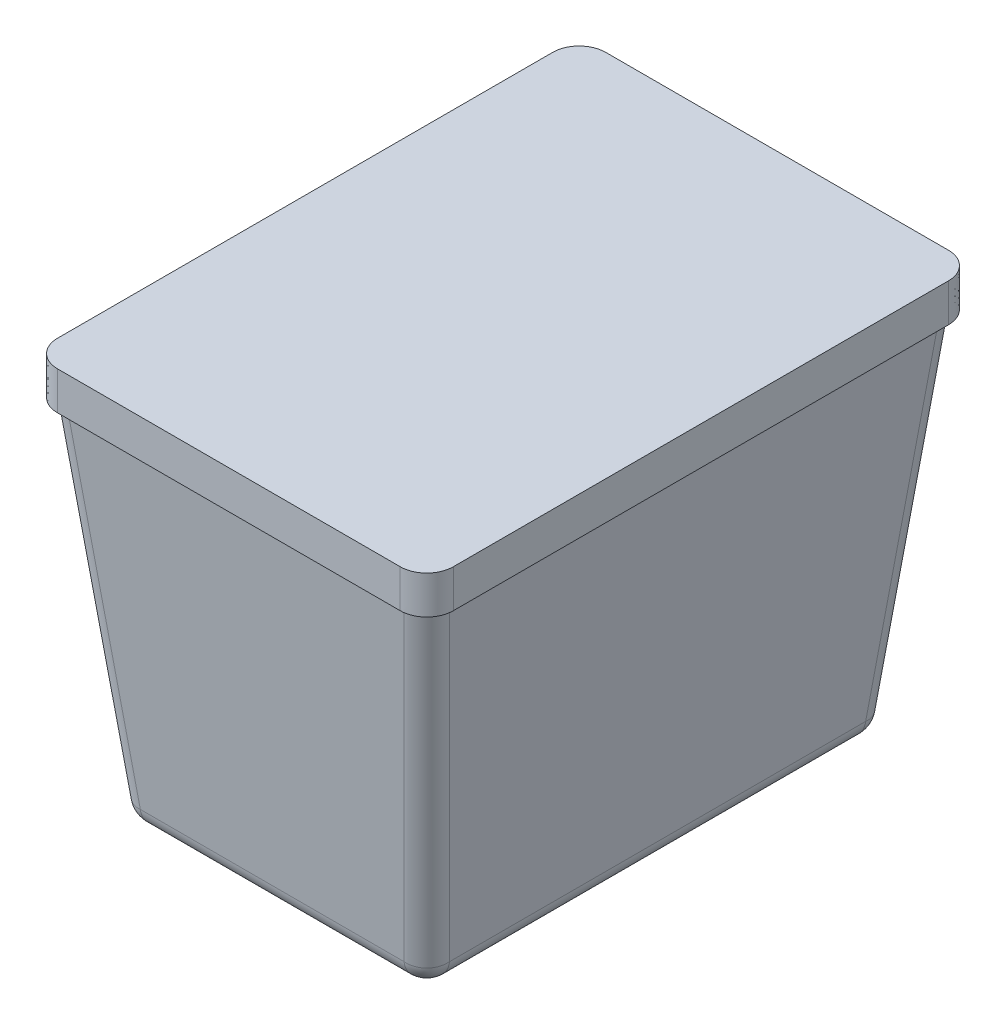
SolidWorks part; units mm, degrees
ref_plane "Alzado" through (0, 0, 0) normal (0, 0, 1) x (1, 0, 0)
ref_plane "Planta" through (0, 0, 0) normal (0, 1, 0) x (1, 0, 0)
ref_plane "Vista lateral" through (0, 0, 0) normal (1, 0, 0) x (0, 0, -1)
sketch "Croquis1" plane through (0, 0, 0) normal (0, 1, 0) x (1, 0, 0)
  line L1 (200, -300) -> (-200, -300)
  line L2 (200, -300) -> (200, 300)
  line L3 (200, 300) -> (-200, 300)
  line L4 (-200, -300) -> (-200, 300)
  line L5 (200, -300) -> (-200, 300) construction
  line L6 (200, 300) -> (-200, -300) construction
  point P0 (0, 0)
  dimension "D1" = 600
  dimension "D2" = 400
extrude "Extruir1" add sketch "Croquis1" along normal blind 520 draft 6 draft outward yes
fillet "Redondeo1" radius 30 8 edges at (0, 0, 300) (200, 0, 0) (0, 0, -300) (-200, 0, 0) (-227.3271, 260, -327.3271) (227.3271, 260, -327.3271) (227.3271, 260, 327.3271) (-227.3271, 260, 327.3271)
shell "Vaciado1" thickness 10 removed face at (0, 520, 0)
sketch "Croquis2" plane through (0, 520, 0) normal (0, 1, 0) x (1, 0, 0)
  line L24 (224.8185, 359.6542) -> (-224.8185, 359.6542)
  line L25 (259.6542, -324.8185) -> (259.6542, 324.8185)
  line L26 (-224.8185, -359.6542) -> (224.8185, -359.6542)
  line L27 (-259.6542, 324.8185) -> (-259.6542, -324.8185)
  line L28 (224.8185, 359.6542) -> (-224.8185, 359.6542)
  line L29 (259.6542, -324.8185) -> (259.6542, 324.8185)
  line L30 (-224.8185, -359.6542) -> (224.8185, -359.6542)
  line L31 (-259.6542, 324.8185) -> (-259.6542, -324.8185)
  spline S0 degree 3 poles (409.626, -1532.0878) (32.0766, -0.852) (-135.9095, 377.862) (-232.7137, 358.7732) (-233.8149, 358.5002) (-235.4515, 358.0079) (-235.9946, 357.83) (-237.0755, 357.446) (-237.6138, 357.2397) (-240.2615, 356.1489) (-242.2653, 355.0812) (-245.1032, 353.1931) (-246.0209, 352.5157) (-247.3539, 351.425) (-247.7906, 351.0493) (-248.6395, 350.2812) (-249.053, 349.888) (-251.067, 347.8765) (-252.5079, 346.1233) (-254.4118, 343.2761) (-255.0058, 342.2851) (-256.0832, 340.2672) (-256.5688, 339.238) (-257.8704, 336.0912) (-258.5327, 333.9145) (-284.6397, 202.615) (424.9986, 1.0365) (1649.82, -251.3643) knots -5.25859 -5.25859 -5.25859 -5.25859 0.125 0.125 0.1875 0.1875 0.21875 0.21875 0.25 0.25 0.375 0.375 0.4375 0.4375 0.46875 0.46875 0.5 0.5 0.625 0.625 0.6875 0.6875 0.75 0.75 0.875 0.875 8.020589 8.020589 8.020589 8.020589 only from (-224.8185, 359.6542) to (-259.6542, 324.8185)
  spline S1 degree 3 poles (-1632.0878, -309.626) (-100.852, 67.9234) (277.862, 235.9095) (258.7732, 332.7137) (258.5002, 333.8149) (258.0079, 335.4515) (257.83, 335.9946) (257.446, 337.0755) (257.2397, 337.6138) (256.1489, 340.2615) (255.0812, 342.2653) (253.1931, 345.1032) (252.5157, 346.0209) (251.425, 347.3539) (251.0493, 347.7906) (250.2812, 348.6395) (249.888, 349.053) (247.8765, 351.067) (246.1233, 352.5079) (243.2761, 354.4118) (242.2851, 355.0058) (240.2672, 356.0832) (239.238, 356.5688) (236.0912, 357.8704) (233.9145, 358.5327) (102.615, 384.6397) (-98.9635, -324.9986) (-351.3643, -1549.82) knots -5.25859 -5.25859 -5.25859 -5.25859 0.125 0.125 0.1875 0.1875 0.21875 0.21875 0.25 0.25 0.375 0.375 0.4375 0.4375 0.46875 0.46875 0.5 0.5 0.625 0.625 0.6875 0.6875 0.75 0.75 0.875 0.875 8.020589 8.020589 8.020589 8.020589 only from (259.6542, 324.8185) to (224.8185, 359.6542)
  spline S2 degree 3 poles (-409.626, 1532.0878) (-32.0766, 0.852) (135.9095, -377.862) (232.7137, -358.7732) (233.8149, -358.5002) (235.4515, -358.0079) (235.9946, -357.83) (237.0755, -357.446) (237.6138, -357.2397) (240.2615, -356.1489) (242.2653, -355.0812) (245.1032, -353.1931) (246.0209, -352.5157) (247.3539, -351.425) (247.7906, -351.0493) (248.6395, -350.2812) (249.053, -349.888) (251.067, -347.8765) (252.5079, -346.1233) (254.4118, -343.2761) (255.0058, -342.2851) (256.0832, -340.2672) (256.5688, -339.238) (257.8704, -336.0912) (258.5327, -333.9145) (284.6397, -202.615) (-424.9986, -1.0365) (-1649.82, 251.3643) knots -5.25859 -5.25859 -5.25859 -5.25859 0.125 0.125 0.1875 0.1875 0.21875 0.21875 0.25 0.25 0.375 0.375 0.4375 0.4375 0.46875 0.46875 0.5 0.5 0.625 0.625 0.6875 0.6875 0.75 0.75 0.875 0.875 8.020589 8.020589 8.020589 8.020589 only from (224.8185, -359.6542) to (259.6542, -324.8185)
  spline S3 degree 3 poles (1632.0878, 309.626) (100.852, -67.9234) (-277.862, -235.9095) (-258.7732, -332.7137) (-258.5002, -333.8149) (-258.0079, -335.4515) (-257.83, -335.9946) (-257.446, -337.0755) (-257.2397, -337.6138) (-256.1489, -340.2615) (-255.0812, -342.2653) (-253.1931, -345.1032) (-252.5157, -346.0209) (-251.425, -347.3539) (-251.0493, -347.7906) (-250.2812, -348.6395) (-249.888, -349.053) (-247.8765, -351.067) (-246.1233, -352.5079) (-243.2761, -354.4118) (-242.2851, -355.0058) (-240.2672, -356.0832) (-239.238, -356.5688) (-236.0912, -357.8704) (-233.9145, -358.5327) (-102.615, -384.6397) (98.9635, 324.9986) (351.3643, 1549.82) knots -5.25859 -5.25859 -5.25859 -5.25859 0.125 0.125 0.1875 0.1875 0.21875 0.21875 0.25 0.25 0.375 0.375 0.4375 0.4375 0.46875 0.46875 0.5 0.5 0.625 0.625 0.6875 0.6875 0.75 0.75 0.875 0.875 8.020589 8.020589 8.020589 8.020589 only from (-259.6542, -324.8185) to (-224.8185, -359.6542)
  spline S4 degree 3 poles (-224.8185, 359.6542) (-227.1201, 359.6542) (-229.3809, 359.4304) (-232.7137, 358.7732) (-233.8149, 358.5002) (-235.4515, 358.0079) (-235.9946, 357.83) (-237.0755, 357.446) (-237.6138, 357.2397) (-240.2615, 356.1489) (-242.2653, 355.0812) (-245.1032, 353.1931) (-246.0209, 352.5157) (-247.3539, 351.425) (-247.7906, 351.0493) (-248.6395, 350.2812) (-249.053, 349.888) (-251.067, 347.8765) (-252.5079, 346.1233) (-254.4118, 343.2761) (-255.0058, 342.2851) (-256.0832, 340.2672) (-256.5688, 339.238) (-257.8704, 336.0912) (-258.5327, 333.9145) (-259.4304, 329.3998) (-259.6542, 327.1202) (-259.6542, 324.8185) knots 0 0 0 0 0.125 0.125 0.1875 0.1875 0.21875 0.21875 0.25 0.25 0.375 0.375 0.4375 0.4375 0.46875 0.46875 0.5 0.5 0.625 0.625 0.6875 0.6875 0.75 0.75 0.875 0.875 1 1 1 1
  spline S5 degree 3 poles (259.6542, 324.8185) (259.6542, 327.1201) (259.4304, 329.3809) (258.7732, 332.7137) (258.5002, 333.8149) (258.0079, 335.4515) (257.83, 335.9946) (257.446, 337.0755) (257.2397, 337.6138) (256.1489, 340.2615) (255.0812, 342.2653) (253.1931, 345.1032) (252.5157, 346.0209) (251.425, 347.3539) (251.0493, 347.7906) (250.2812, 348.6395) (249.888, 349.053) (247.8765, 351.067) (246.1233, 352.5079) (243.2761, 354.4118) (242.2851, 355.0058) (240.2672, 356.0832) (239.238, 356.5688) (236.0912, 357.8704) (233.9145, 358.5327) (229.3998, 359.4304) (227.1202, 359.6542) (224.8185, 359.6542) knots 0 0 0 0 0.125 0.125 0.1875 0.1875 0.21875 0.21875 0.25 0.25 0.375 0.375 0.4375 0.4375 0.46875 0.46875 0.5 0.5 0.625 0.625 0.6875 0.6875 0.75 0.75 0.875 0.875 1 1 1 1
  spline S6 degree 3 poles (224.8185, -359.6542) (227.1201, -359.6542) (229.3809, -359.4304) (232.7137, -358.7732) (233.8149, -358.5002) (235.4515, -358.0079) (235.9946, -357.83) (237.0755, -357.446) (237.6138, -357.2397) (240.2615, -356.1489) (242.2653, -355.0812) (245.1032, -353.1931) (246.0209, -352.5157) (247.3539, -351.425) (247.7906, -351.0493) (248.6395, -350.2812) (249.053, -349.888) (251.067, -347.8765) (252.5079, -346.1233) (254.4118, -343.2761) (255.0058, -342.2851) (256.0832, -340.2672) (256.5688, -339.238) (257.8704, -336.0912) (258.5327, -333.9145) (259.4304, -329.3998) (259.6542, -327.1202) (259.6542, -324.8185) knots 0 0 0 0 0.125 0.125 0.1875 0.1875 0.21875 0.21875 0.25 0.25 0.375 0.375 0.4375 0.4375 0.46875 0.46875 0.5 0.5 0.625 0.625 0.6875 0.6875 0.75 0.75 0.875 0.875 1 1 1 1
  spline S7 degree 3 poles (-259.6542, -324.8185) (-259.6542, -327.1201) (-259.4304, -329.3809) (-258.7732, -332.7137) (-258.5002, -333.8149) (-258.0079, -335.4515) (-257.83, -335.9946) (-257.446, -337.0755) (-257.2397, -337.6138) (-256.1489, -340.2615) (-255.0812, -342.2653) (-253.1931, -345.1032) (-252.5157, -346.0209) (-251.425, -347.3539) (-251.0493, -347.7906) (-250.2812, -348.6395) (-249.888, -349.053) (-247.8765, -351.067) (-246.1233, -352.5079) (-243.2761, -354.4118) (-242.2851, -355.0058) (-240.2672, -356.0832) (-239.238, -356.5688) (-236.0912, -357.8704) (-233.9145, -358.5327) (-229.3998, -359.4304) (-227.1202, -359.6542) (-224.8185, -359.6542) knots 0 0 0 0 0.125 0.125 0.1875 0.1875 0.21875 0.21875 0.25 0.25 0.375 0.375 0.4375 0.4375 0.46875 0.46875 0.5 0.5 0.625 0.625 0.6875 0.6875 0.75 0.75 0.875 0.875 1 1 1 1
  dimension "D1" = 5
extrude "Extruir2" add sketch "Croquis2" against normal blind 40 separate body
sketch "Croquis3" plane through (0, 520, 0) normal (0, 1, 0) x (1, 0, 0)
  line L4 (-259.6542, 324.8185) -> (-259.6542, -324.8185)
  line L5 (-224.8185, -359.6542) -> (224.8185, -359.6542)
  line L6 (259.6542, -324.8185) -> (259.6542, 324.8185)
  line L7 (224.8185, 359.6542) -> (-224.8185, 359.6542)
  line L8 (-259.6542, 324.8185) -> (-259.6542, -324.8185)
  line L9 (-224.8185, -359.6542) -> (224.8185, -359.6542)
  line L10 (259.6542, -324.8185) -> (259.6542, 324.8185)
  line L11 (224.8185, 359.6542) -> (-224.8185, 359.6542)
  spline S4 degree 3 poles (409.626, -1532.0878) (32.0766, -0.852) (-135.9095, 377.862) (-232.7137, 358.7732) (-233.8149, 358.5002) (-235.4515, 358.0079) (-235.9946, 357.83) (-237.0755, 357.446) (-237.6138, 357.2397) (-240.2615, 356.1489) (-242.2653, 355.0812) (-245.1032, 353.1931) (-246.0209, 352.5157) (-247.3539, 351.425) (-247.7906, 351.0493) (-248.6395, 350.2812) (-249.053, 349.888) (-251.067, 347.8765) (-252.5079, 346.1233) (-254.4118, 343.2761) (-255.0058, 342.2851) (-256.0832, 340.2672) (-256.5688, 339.238) (-257.8704, 336.0912) (-258.5327, 333.9145) (-284.6397, 202.615) (424.9986, 1.0365) (1649.82, -251.3643) knots -5.25859 -5.25859 -5.25859 -5.25859 0.125 0.125 0.1875 0.1875 0.21875 0.21875 0.25 0.25 0.375 0.375 0.4375 0.4375 0.46875 0.46875 0.5 0.5 0.625 0.625 0.6875 0.6875 0.75 0.75 0.875 0.875 8.020589 8.020589 8.020589 8.020589 only from (-224.8185, 359.6542) to (-259.6542, 324.8185)
  spline S5 degree 3 poles (1632.0878, 309.626) (100.852, -67.9234) (-277.862, -235.9095) (-258.7732, -332.7137) (-258.5002, -333.8149) (-258.0079, -335.4515) (-257.83, -335.9946) (-257.446, -337.0755) (-257.2397, -337.6138) (-256.1489, -340.2615) (-255.0812, -342.2653) (-253.1931, -345.1032) (-252.5157, -346.0209) (-251.425, -347.3539) (-251.0493, -347.7906) (-250.2812, -348.6395) (-249.888, -349.053) (-247.8765, -351.067) (-246.1233, -352.5079) (-243.2761, -354.4118) (-242.2851, -355.0058) (-240.2672, -356.0832) (-239.238, -356.5688) (-236.0912, -357.8704) (-233.9145, -358.5327) (-102.615, -384.6397) (98.9635, 324.9986) (351.3643, 1549.82) knots -5.25859 -5.25859 -5.25859 -5.25859 0.125 0.125 0.1875 0.1875 0.21875 0.21875 0.25 0.25 0.375 0.375 0.4375 0.4375 0.46875 0.46875 0.5 0.5 0.625 0.625 0.6875 0.6875 0.75 0.75 0.875 0.875 8.020589 8.020589 8.020589 8.020589 only from (-259.6542, -324.8185) to (-224.8185, -359.6542)
  spline S6 degree 3 poles (-409.626, 1532.0878) (-32.0766, 0.852) (135.9095, -377.862) (232.7137, -358.7732) (233.8149, -358.5002) (235.4515, -358.0079) (235.9946, -357.83) (237.0755, -357.446) (237.6138, -357.2397) (240.2615, -356.1489) (242.2653, -355.0812) (245.1032, -353.1931) (246.0209, -352.5157) (247.3539, -351.425) (247.7906, -351.0493) (248.6395, -350.2812) (249.053, -349.888) (251.067, -347.8765) (252.5079, -346.1233) (254.4118, -343.2761) (255.0058, -342.2851) (256.0832, -340.2672) (256.5688, -339.238) (257.8704, -336.0912) (258.5327, -333.9145) (284.6397, -202.615) (-424.9986, -1.0365) (-1649.82, 251.3643) knots -5.25859 -5.25859 -5.25859 -5.25859 0.125 0.125 0.1875 0.1875 0.21875 0.21875 0.25 0.25 0.375 0.375 0.4375 0.4375 0.46875 0.46875 0.5 0.5 0.625 0.625 0.6875 0.6875 0.75 0.75 0.875 0.875 8.020589 8.020589 8.020589 8.020589 only from (224.8185, -359.6542) to (259.6542, -324.8185)
  spline S7 degree 3 poles (-1632.0878, -309.626) (-100.852, 67.9234) (277.862, 235.9095) (258.7732, 332.7137) (258.5002, 333.8149) (258.0079, 335.4515) (257.83, 335.9946) (257.446, 337.0755) (257.2397, 337.6138) (256.1489, 340.2615) (255.0812, 342.2653) (253.1931, 345.1032) (252.5157, 346.0209) (251.425, 347.3539) (251.0493, 347.7906) (250.2812, 348.6395) (249.888, 349.053) (247.8765, 351.067) (246.1233, 352.5079) (243.2761, 354.4118) (242.2851, 355.0058) (240.2672, 356.0832) (239.238, 356.5688) (236.0912, 357.8704) (233.9145, 358.5327) (102.615, 384.6397) (-98.9635, -324.9986) (-351.3643, -1549.82) knots -5.25859 -5.25859 -5.25859 -5.25859 0.125 0.125 0.1875 0.1875 0.21875 0.21875 0.25 0.25 0.375 0.375 0.4375 0.4375 0.46875 0.46875 0.5 0.5 0.625 0.625 0.6875 0.6875 0.75 0.75 0.875 0.875 8.020589 8.020589 8.020589 8.020589 only from (259.6542, 324.8185) to (224.8185, 359.6542)
  spline S8 degree 3 poles (-224.8185, 359.6542) (-227.1201, 359.6542) (-229.3809, 359.4304) (-232.7137, 358.7732) (-233.8149, 358.5002) (-235.4515, 358.0079) (-235.9946, 357.83) (-237.0755, 357.446) (-237.6138, 357.2397) (-240.2615, 356.1489) (-242.2653, 355.0812) (-245.1032, 353.1931) (-246.0209, 352.5157) (-247.3539, 351.425) (-247.7906, 351.0493) (-248.6395, 350.2812) (-249.053, 349.888) (-251.067, 347.8765) (-252.5079, 346.1233) (-254.4118, 343.2761) (-255.0058, 342.2851) (-256.0832, 340.2672) (-256.5688, 339.238) (-257.8704, 336.0912) (-258.5327, 333.9145) (-259.4304, 329.3998) (-259.6542, 327.1202) (-259.6542, 324.8185) knots 0 0 0 0 0.125 0.125 0.1875 0.1875 0.21875 0.21875 0.25 0.25 0.375 0.375 0.4375 0.4375 0.46875 0.46875 0.5 0.5 0.625 0.625 0.6875 0.6875 0.75 0.75 0.875 0.875 1 1 1 1
  spline S9 degree 3 poles (-259.6542, -324.8185) (-259.6542, -327.1201) (-259.4304, -329.3809) (-258.7732, -332.7137) (-258.5002, -333.8149) (-258.0079, -335.4515) (-257.83, -335.9946) (-257.446, -337.0755) (-257.2397, -337.6138) (-256.1489, -340.2615) (-255.0812, -342.2653) (-253.1931, -345.1032) (-252.5157, -346.0209) (-251.425, -347.3539) (-251.0493, -347.7906) (-250.2812, -348.6395) (-249.888, -349.053) (-247.8765, -351.067) (-246.1233, -352.5079) (-243.2761, -354.4118) (-242.2851, -355.0058) (-240.2672, -356.0832) (-239.238, -356.5688) (-236.0912, -357.8704) (-233.9145, -358.5327) (-229.3998, -359.4304) (-227.1202, -359.6542) (-224.8185, -359.6542) knots 0 0 0 0 0.125 0.125 0.1875 0.1875 0.21875 0.21875 0.25 0.25 0.375 0.375 0.4375 0.4375 0.46875 0.46875 0.5 0.5 0.625 0.625 0.6875 0.6875 0.75 0.75 0.875 0.875 1 1 1 1
  spline S10 degree 3 poles (224.8185, -359.6542) (227.1201, -359.6542) (229.3809, -359.4304) (232.7137, -358.7732) (233.8149, -358.5002) (235.4515, -358.0079) (235.9946, -357.83) (237.0755, -357.446) (237.6138, -357.2397) (240.2615, -356.1489) (242.2653, -355.0812) (245.1032, -353.1931) (246.0209, -352.5157) (247.3539, -351.425) (247.7906, -351.0493) (248.6395, -350.2812) (249.053, -349.888) (251.067, -347.8765) (252.5079, -346.1233) (254.4118, -343.2761) (255.0058, -342.2851) (256.0832, -340.2672) (256.5688, -339.238) (257.8704, -336.0912) (258.5327, -333.9145) (259.4304, -329.3998) (259.6542, -327.1202) (259.6542, -324.8185) knots 0 0 0 0 0.125 0.125 0.1875 0.1875 0.21875 0.21875 0.25 0.25 0.375 0.375 0.4375 0.4375 0.46875 0.46875 0.5 0.5 0.625 0.625 0.6875 0.6875 0.75 0.75 0.875 0.875 1 1 1 1
  spline S11 degree 3 poles (259.6542, 324.8185) (259.6542, 327.1201) (259.4304, 329.3809) (258.7732, 332.7137) (258.5002, 333.8149) (258.0079, 335.4515) (257.83, 335.9946) (257.446, 337.0755) (257.2397, 337.6138) (256.1489, 340.2615) (255.0812, 342.2653) (253.1931, 345.1032) (252.5157, 346.0209) (251.425, 347.3539) (251.0493, 347.7906) (250.2812, 348.6395) (249.888, 349.053) (247.8765, 351.067) (246.1233, 352.5079) (243.2761, 354.4118) (242.2851, 355.0058) (240.2672, 356.0832) (239.238, 356.5688) (236.0912, 357.8704) (233.9145, 358.5327) (229.3998, 359.4304) (227.1202, 359.6542) (224.8185, 359.6542) knots 0 0 0 0 0.125 0.125 0.1875 0.1875 0.21875 0.21875 0.25 0.25 0.375 0.375 0.4375 0.4375 0.46875 0.46875 0.5 0.5 0.625 0.625 0.6875 0.6875 0.75 0.75 0.875 0.875 1 1 1 1
  dimension "D1" = 0
extrude "Extruir3" add sketch "Croquis3" along normal blind 10
